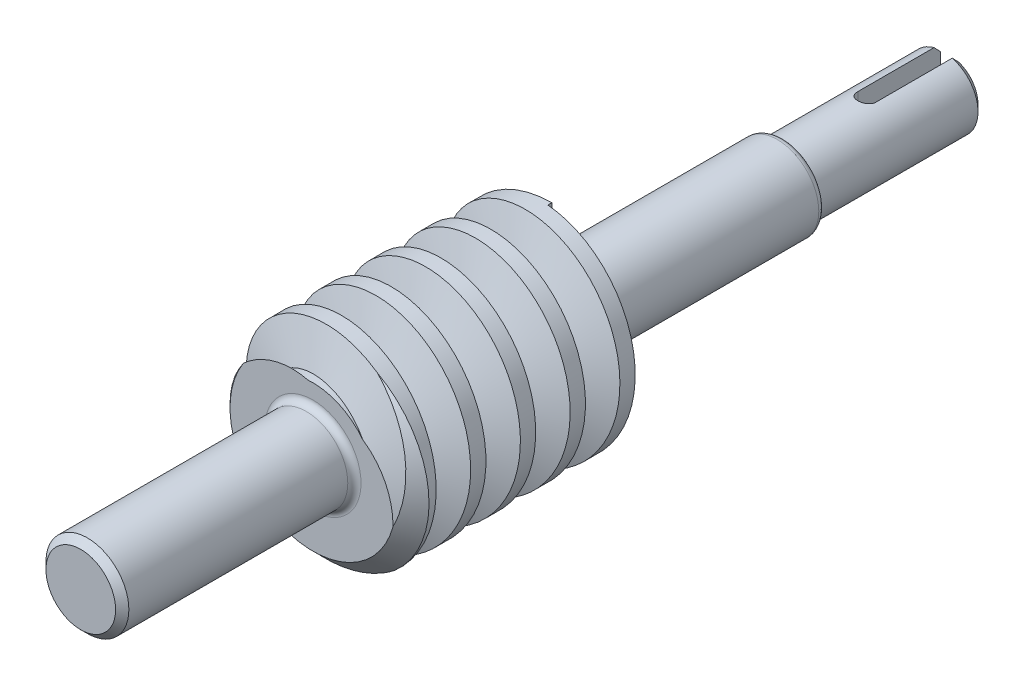
SolidWorks part; units mm, degrees
material "1.4000 (X6Cr13)"
ref_plane "Ön Düzlem" through (0, 0, 0) normal (0, 0, 1) x (1, 0, 0)
ref_plane "Üst Düzlem" through (0, 0, 0) normal (0, 1, 0) x (1, 0, 0)
ref_plane "Sağ Düzlem" through (0, 0, 0) normal (1, 0, 0) x (0, 0, -1)
sketch "Sketch1" plane through (0, 0, 0) normal (0, 0, 1) x (1, 0, 0)
  circle A0 centre (0, 0) radius 30
  dimension "D1" = 60
extrude "Boss-Extrude1" add sketch "Sketch1" along normal mid plane 72
chamfer "Chamfer1" distance 5 angle 45 1 edges at (30, 0, 36)
sketch "Sketch2" plane through (0, 0, 0) normal (1, 0, 0) x (0, 0, -1)
  line L0 (36, 0) -> (-50, 0) construction
  line L1 (36, -30) -> (36, 30) construction
  line L2 (-50, 0) -> (-50, 34) construction
  line L3 (-56.6498, 34) -> (-43.3502, 34)
  line L4 (-43.3502, 34) -> (-48.8098, 19)
  line L5 (-48.8098, 19) -> (-51.1902, 19)
  line L6 (-46.08, 26.5) -> (-50, 26.5) construction
  line L7 (-56.6498, 34) -> (-51.1902, 19)
  point P9 (-50, 34)
  point P12 (-50, 19)
  dimension "D1" = 20
  dimension "D2" = 15
  dimension "D3" = 50
  dimension "D4" = 19
  dimension "D5" = 3.92
ref_plane "Plane1" through (0, 0, 48.8098) normal (0, 0, 1) x (1, 0, 0)
sketch "Sketch3" plane through (0, 0, 48.8098) normal (0, 0, 1) x (1, 0, 0)
  circle A0 centre (0, 0) radius 30
  circle A1 centre (0, 0) radius 30 construction
curve "Helix/Spiral1" pitch 15 height 90 radius 30 left hand yes centre (0, 0, 48.8098) axis (0, 0, -1) start towards (0, 1, 0)
sweep "Cut-Sweep1" cut profiles "Sketch2" path "Helix/Spiral1" align with end faces yes
sketch "Sketch4" plane through (0, 0, 36) normal (0, 0, 1) x (1, 0, 0)
  circle A0 centre (0, 0) radius 12.5
  dimension "D1" = 25
extrude "Boss-Extrude2" add sketch "Sketch4" along normal blind 70 and the other way blind 142
sketch "Sketch5" plane through (0, 0, -106) normal (0, 0, -1) x (-1, 0, 0)
  circle A0 centre (0, 0) radius 10.5
  circle A1 centre (0, 0) radius 12.5
  circle A2 centre (0, 0) radius 12.5 construction
  dimension "D1" = 0
  dimension "D2" = 2
extrude "Boss-Extrude3" add sketch "Sketch5" along normal blind 50
fillet "Fillet1" radius 2 3 edges at (12.5, 0, -106) (12.5, 0, -36) (12.5, 0, 36)
chamfer "Chamfer2" distance 2 angle 45 2 edges at (-10.5, 0, -156) (12.5, 0, 106)
sketch "Sketch6" plane through (0, 0, 0) normal (0, 1, 0) x (1, 0, 0)
  line L0 (0, 159.768) -> (0, 131) construction
  line L1 (2.75, 159.768) -> (2.75, 131)
  line L2 (-2.75, 159.768) -> (-2.75, 131)
  line L3 (8.5, 156) -> (-8.5, 156) construction
  arc A0 (2.75, 159.768) -> (-2.75, 159.768) centre (0, 159.768) ccw
  arc A1 (-2.75, 131) -> (2.75, 131) centre (0, 131) ccw
  point P3 (0, 145.384)
  dimension "D1" = 25
  dimension "D2" = 5.5
extrude "Cut-Extrude1" cut sketch "Sketch6" along normal blind 50
